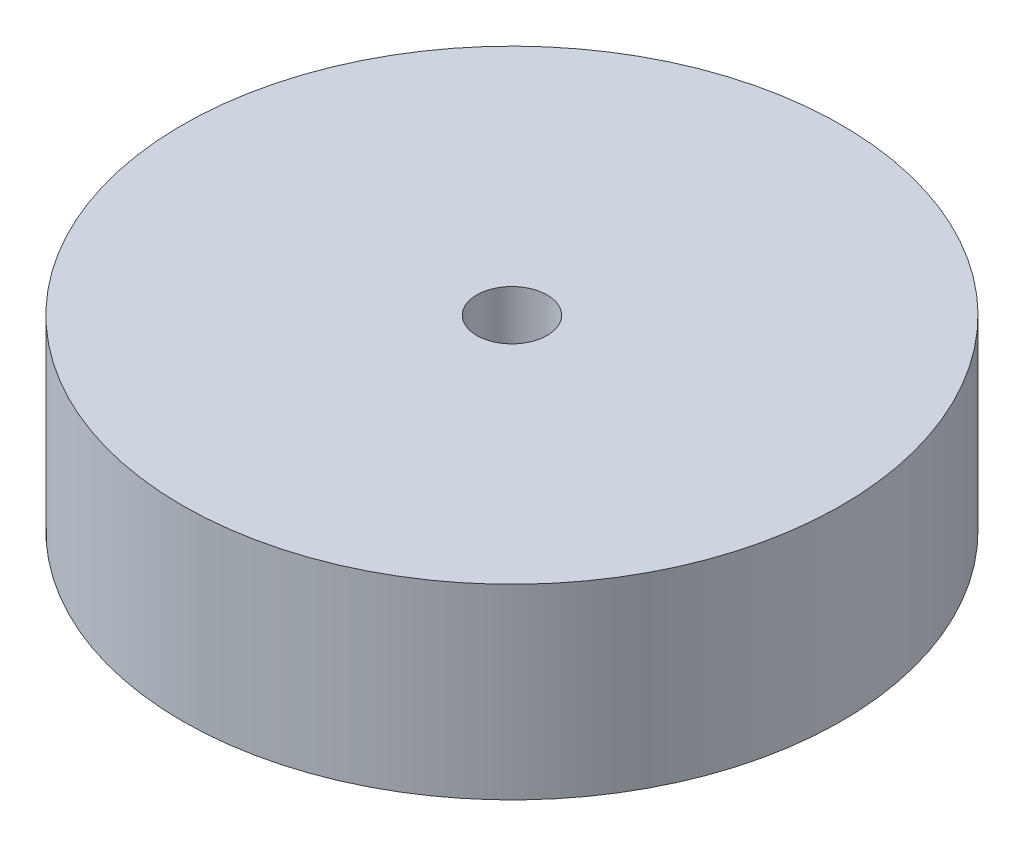
SolidWorks part; units mm, degrees
ref_plane "Front Plane" through (0, 0, 0) normal (0, 0, 1) x (1, 0, 0)
ref_plane "Top Plane" through (0, 0, 0) normal (0, 1, 0) x (1, 0, 0)
ref_plane "Right Plane" through (0, 0, 0) normal (1, 0, 0) x (0, 0, -1)
sketch "Sketch1" plane through (0, 0, 0) normal (0, 1, 0) x (1, 0, 0)
  circle A0 centre (0, 0) radius 1.6
  circle A1 centre (0, 0) radius 15
  dimension "D1" = 30
  dimension "D2" = 3.2
extrude "Boss-Extrude1" add sketch "Sketch1" along normal blind 8.5
